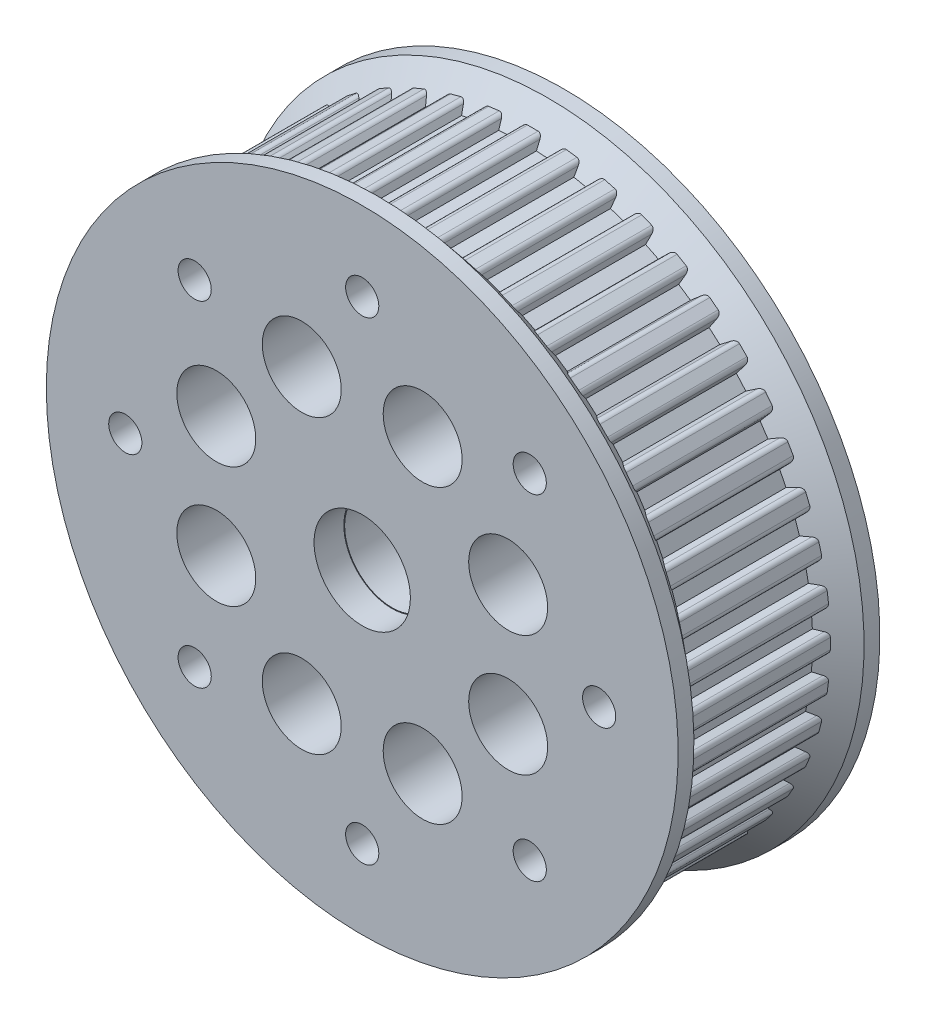
SolidWorks part; units mm, degrees
ref_plane "Plan de face" through (0, 0, 0) normal (0, 0, 1) x (1, 0, 0)
ref_plane "Plan de dessus" through (0, 0, 0) normal (0, 1, 0) x (1, 0, 0)
ref_plane "Plan de droite" through (0, 0, 0) normal (1, 0, 0) x (0, 0, -1)
sketch "Esquisse1" plane through (0, 0, 0) normal (0, 0, 1) x (1, 0, 0)
  line L0 (0, 0) -> (0, 38.195) construction
  line L1 (0, 0) -> (4.9854, 37.8682) construction
  line L2 (1.4855, 36.4258) -> (3.2817, 36.3081)
  line L3 (0, 0) -> (2.3836, 36.367) construction
  line L4 (0, 37.6783) -> (0.6704, 37.6783)
  line L5 (1.2464, 37.2462) -> (1.4855, 36.4258)
  line L6 (4.918, 37.356) -> (4.2534, 37.4435)
  line L7 (3.6259, 37.0903) -> (3.2817, 36.3081)
  line L8 (6.2274, 35.9203) -> (7.9928, 35.5691)
  line L9 (4.918, 37.356) -> (5.5827, 37.2685)
  line L10 (6.0974, 36.7649) -> (6.2274, 35.9203)
  line L11 (9.7519, 36.3945) -> (9.1043, 36.568)
  line L12 (8.4361, 36.2997) -> (7.9928, 35.5691)
  line L13 (10.8626, 34.8002) -> (12.5671, 34.2216)
  line L14 (9.7519, 36.3945) -> (10.3994, 36.221)
  line L15 (10.844, 35.6545) -> (10.8626, 34.8002)
  line L16 (14.4189, 34.8103) -> (13.7995, 35.0668)
  line L17 (13.102, 34.888) -> (12.5671, 34.2216)
  line L18 (15.312, 33.0846) -> (16.9264, 32.2885)
  line L19 (14.4189, 34.8103) -> (15.0382, 34.5537)
  line L20 (15.4051, 33.9341) -> (15.312, 33.0846)
  line L21 (18.8392, 32.6304) -> (18.2586, 32.9656)
  line L22 (17.5437, 32.8794) -> (16.9264, 32.2885)
  line L23 (19.4994, 30.8029) -> (20.9961, 29.8029)
  line L24 (18.8392, 32.6304) -> (19.4197, 32.2952)
  line L25 (19.7025, 31.633) -> (19.4994, 30.8029)
  line L26 (22.9371, 29.8922) -> (22.4053, 30.3003)
  line L27 (21.6852, 30.3082) -> (20.9961, 29.8029)
  line L28 (23.3532, 27.9942) -> (24.7065, 26.8074)
  line L29 (22.9371, 29.8922) -> (23.469, 29.4841)
  line L30 (23.6629, 28.7907) -> (23.3532, 27.9942)
  line L31 (26.6426, 26.6426) -> (26.1686, 27.1166)
  line L32 (25.4557, 27.2184) -> (24.7065, 26.8074)
  line L33 (26.8074, 24.7065) -> (27.9942, 23.3532)
  line L34 (26.6426, 26.6426) -> (27.1166, 26.1686)
  line L35 (27.2184, 25.4557) -> (26.8074, 24.7065)
  line L36 (29.8922, 22.9371) -> (29.4841, 23.469)
  line L37 (28.7907, 23.6629) -> (27.9942, 23.3532)
  line L38 (29.8029, 20.9961) -> (30.8029, 19.4994)
  line L39 (29.8922, 22.9371) -> (30.3003, 22.4053)
  line L40 (30.3082, 21.6852) -> (29.8029, 20.9961)
  line L41 (32.6304, 18.8392) -> (32.2952, 19.4197)
  line L42 (31.633, 19.7025) -> (30.8029, 19.4994)
  line L43 (32.2885, 16.9264) -> (33.0846, 15.312)
  line L44 (32.6304, 18.8392) -> (32.9656, 18.2586)
  line L45 (32.8794, 17.5437) -> (32.2885, 16.9264)
  line L46 (34.8103, 14.4189) -> (34.5537, 15.0382)
  line L47 (33.9341, 15.4051) -> (33.0846, 15.312)
  line L48 (34.2216, 12.5671) -> (34.8002, 10.8626)
  line L49 (34.8103, 14.4189) -> (35.0668, 13.7995)
  line L50 (34.888, 13.102) -> (34.2216, 12.5671)
  line L51 (36.3945, 9.7519) -> (36.221, 10.3994)
  line L52 (35.6545, 10.844) -> (34.8002, 10.8626)
  line L53 (35.5691, 7.9928) -> (35.9203, 6.2274)
  line L54 (36.3945, 9.7519) -> (36.568, 9.1043)
  line L55 (36.2997, 8.4361) -> (35.5691, 7.9928)
  line L56 (37.356, 4.918) -> (37.2685, 5.5827)
  line L57 (36.7649, 6.0974) -> (35.9203, 6.2274)
  line L58 (36.3081, 3.2817) -> (36.4258, 1.4855)
  line L59 (37.356, 4.918) -> (37.4435, 4.2534)
  line L60 (37.0903, 3.6259) -> (36.3081, 3.2817)
  line L61 (37.6783, 0) -> (37.6783, 0.6704)
  line L62 (37.2462, 1.2464) -> (36.4258, 1.4855)
  line L63 (36.4258, -1.4855) -> (36.3081, -3.2817)
  line L64 (37.6783, 0) -> (37.6783, -0.6704)
  line L65 (37.2462, -1.2464) -> (36.4258, -1.4855)
  line L66 (37.356, -4.918) -> (37.4435, -4.2534)
  line L67 (37.0903, -3.6259) -> (36.3081, -3.2817)
  line L68 (35.9203, -6.2274) -> (35.5691, -7.9928)
  line L69 (37.356, -4.918) -> (37.2685, -5.5827)
  line L70 (36.7649, -6.0974) -> (35.9203, -6.2274)
  line L71 (36.3945, -9.7519) -> (36.568, -9.1043)
  line L72 (36.2997, -8.4361) -> (35.5691, -7.9928)
  line L73 (34.8002, -10.8626) -> (34.2216, -12.5671)
  line L74 (36.3945, -9.7519) -> (36.221, -10.3994)
  line L75 (35.6545, -10.844) -> (34.8002, -10.8626)
  line L76 (34.8103, -14.4189) -> (35.0668, -13.7995)
  line L77 (34.888, -13.102) -> (34.2216, -12.5671)
  line L78 (33.0846, -15.312) -> (32.2885, -16.9264)
  line L79 (34.8103, -14.4189) -> (34.5537, -15.0382)
  line L80 (33.9341, -15.4051) -> (33.0846, -15.312)
  line L81 (32.6304, -18.8392) -> (32.9656, -18.2586)
  line L82 (32.8794, -17.5437) -> (32.2885, -16.9264)
  line L83 (30.8029, -19.4994) -> (29.8029, -20.9961)
  line L84 (32.6304, -18.8392) -> (32.2952, -19.4197)
  line L85 (31.633, -19.7025) -> (30.8029, -19.4994)
  line L86 (29.8922, -22.9371) -> (30.3003, -22.4053)
  line L87 (30.3082, -21.6852) -> (29.8029, -20.9961)
  line L88 (27.9942, -23.3532) -> (26.8074, -24.7065)
  line L89 (29.8922, -22.9371) -> (29.4841, -23.469)
  line L90 (28.7907, -23.6629) -> (27.9942, -23.3532)
  line L91 (26.6426, -26.6426) -> (27.1166, -26.1686)
  line L92 (27.2184, -25.4557) -> (26.8074, -24.7065)
  line L93 (24.7065, -26.8074) -> (23.3532, -27.9942)
  line L94 (26.6426, -26.6426) -> (26.1686, -27.1166)
  line L95 (25.4557, -27.2184) -> (24.7065, -26.8074)
  line L96 (22.9371, -29.8922) -> (23.469, -29.4841)
  line L97 (23.6629, -28.7907) -> (23.3532, -27.9942)
  line L98 (20.9961, -29.8029) -> (19.4994, -30.8029)
  line L99 (22.9371, -29.8922) -> (22.4053, -30.3003)
  line L100 (21.6852, -30.3082) -> (20.9961, -29.8029)
  line L101 (18.8392, -32.6304) -> (19.4197, -32.2952)
  line L102 (19.7025, -31.633) -> (19.4994, -30.8029)
  line L103 (16.9264, -32.2885) -> (15.312, -33.0846)
  line L104 (18.8392, -32.6304) -> (18.2586, -32.9656)
  line L105 (17.5437, -32.8794) -> (16.9264, -32.2885)
  line L106 (14.4189, -34.8103) -> (15.0382, -34.5537)
  line L107 (15.4051, -33.9341) -> (15.312, -33.0846)
  line L108 (12.5671, -34.2216) -> (10.8626, -34.8002)
  line L109 (14.4189, -34.8103) -> (13.7995, -35.0668)
  line L110 (13.102, -34.888) -> (12.5671, -34.2216)
  line L111 (9.7519, -36.3945) -> (10.3994, -36.221)
  line L112 (10.844, -35.6545) -> (10.8626, -34.8002)
  line L113 (7.9928, -35.5691) -> (6.2274, -35.9203)
  line L114 (9.7519, -36.3945) -> (9.1043, -36.568)
  line L115 (8.4361, -36.2997) -> (7.9928, -35.5691)
  line L116 (4.918, -37.356) -> (5.5827, -37.2685)
  line L117 (6.0974, -36.7649) -> (6.2274, -35.9203)
  line L118 (3.2817, -36.3081) -> (1.4855, -36.4258)
  line L119 (4.918, -37.356) -> (4.2534, -37.4435)
  line L120 (3.6259, -37.0903) -> (3.2817, -36.3081)
  line L121 (0, -37.6783) -> (0.6704, -37.6783)
  line L122 (1.2464, -37.2462) -> (1.4855, -36.4258)
  line L123 (-1.4855, -36.4258) -> (-3.2817, -36.3081)
  line L124 (0, -37.6783) -> (-0.6704, -37.6783)
  line L125 (-1.2464, -37.2462) -> (-1.4855, -36.4258)
  line L126 (-4.918, -37.356) -> (-4.2534, -37.4435)
  line L127 (-3.6259, -37.0903) -> (-3.2817, -36.3081)
  line L128 (-6.2274, -35.9203) -> (-7.9928, -35.5691)
  line L129 (-4.918, -37.356) -> (-5.5827, -37.2685)
  line L130 (-6.0974, -36.7649) -> (-6.2274, -35.9203)
  line L131 (-9.7519, -36.3945) -> (-9.1043, -36.568)
  line L132 (-8.4361, -36.2997) -> (-7.9928, -35.5691)
  line L133 (-10.8626, -34.8002) -> (-12.5671, -34.2216)
  line L134 (-9.7519, -36.3945) -> (-10.3994, -36.221)
  line L135 (-10.844, -35.6545) -> (-10.8626, -34.8002)
  line L136 (-14.4189, -34.8103) -> (-13.7995, -35.0668)
  line L137 (-13.102, -34.888) -> (-12.5671, -34.2216)
  line L138 (-15.312, -33.0846) -> (-16.9264, -32.2885)
  line L139 (-14.4189, -34.8103) -> (-15.0382, -34.5537)
  line L140 (-15.4051, -33.9341) -> (-15.312, -33.0846)
  line L141 (-18.8392, -32.6304) -> (-18.2586, -32.9656)
  line L142 (-17.5437, -32.8794) -> (-16.9264, -32.2885)
  line L143 (-19.4994, -30.8029) -> (-20.9961, -29.8029)
  line L144 (-18.8392, -32.6304) -> (-19.4197, -32.2952)
  line L145 (-19.7025, -31.633) -> (-19.4994, -30.8029)
  line L146 (-22.9371, -29.8922) -> (-22.4053, -30.3003)
  line L147 (-21.6852, -30.3082) -> (-20.9961, -29.8029)
  line L148 (-23.3532, -27.9942) -> (-24.7065, -26.8074)
  line L149 (-22.9371, -29.8922) -> (-23.469, -29.4841)
  line L150 (-23.6629, -28.7907) -> (-23.3532, -27.9942)
  line L151 (-26.6426, -26.6426) -> (-26.1686, -27.1166)
  line L152 (-25.4557, -27.2184) -> (-24.7065, -26.8074)
  line L153 (-26.8074, -24.7065) -> (-27.9942, -23.3532)
  line L154 (-26.6426, -26.6426) -> (-27.1166, -26.1686)
  line L155 (-27.2184, -25.4557) -> (-26.8074, -24.7065)
  line L156 (-29.8922, -22.9371) -> (-29.4841, -23.469)
  line L157 (-28.7907, -23.6629) -> (-27.9942, -23.3532)
  line L158 (-29.8029, -20.9961) -> (-30.8029, -19.4994)
  line L159 (-29.8922, -22.9371) -> (-30.3003, -22.4053)
  line L160 (-30.3082, -21.6852) -> (-29.8029, -20.9961)
  line L161 (-32.6304, -18.8392) -> (-32.2952, -19.4197)
  line L162 (-31.633, -19.7025) -> (-30.8029, -19.4994)
  line L163 (-32.2885, -16.9264) -> (-33.0846, -15.312)
  line L164 (-32.6304, -18.8392) -> (-32.9656, -18.2586)
  line L165 (-32.8794, -17.5437) -> (-32.2885, -16.9264)
  line L166 (-34.8103, -14.4189) -> (-34.5537, -15.0382)
  line L167 (-33.9341, -15.4051) -> (-33.0846, -15.312)
  line L168 (-34.2216, -12.5671) -> (-34.8002, -10.8626)
  line L169 (-34.8103, -14.4189) -> (-35.0668, -13.7995)
  line L170 (-34.888, -13.102) -> (-34.2216, -12.5671)
  line L171 (-36.3945, -9.7519) -> (-36.221, -10.3994)
  line L172 (-35.6545, -10.844) -> (-34.8002, -10.8626)
  line L173 (-35.5691, -7.9928) -> (-35.9203, -6.2274)
  line L174 (-36.3945, -9.7519) -> (-36.568, -9.1043)
  line L175 (-36.2997, -8.4361) -> (-35.5691, -7.9928)
  line L176 (-37.356, -4.918) -> (-37.2685, -5.5827)
  line L177 (-36.7649, -6.0974) -> (-35.9203, -6.2274)
  line L178 (-36.3081, -3.2817) -> (-36.4258, -1.4855)
  line L179 (-37.356, -4.918) -> (-37.4435, -4.2534)
  line L180 (-37.0903, -3.6259) -> (-36.3081, -3.2817)
  line L181 (-37.6783, 0) -> (-37.6783, -0.6704)
  line L182 (-37.2462, -1.2464) -> (-36.4258, -1.4855)
  line L183 (-36.4258, 1.4855) -> (-36.3081, 3.2817)
  line L184 (-37.6783, 0) -> (-37.6783, 0.6704)
  line L185 (-37.2462, 1.2464) -> (-36.4258, 1.4855)
  line L186 (-37.356, 4.918) -> (-37.4435, 4.2534)
  line L187 (-37.0903, 3.6259) -> (-36.3081, 3.2817)
  line L188 (-35.9203, 6.2274) -> (-35.5691, 7.9928)
  line L189 (-37.356, 4.918) -> (-37.2685, 5.5827)
  line L190 (-36.7649, 6.0974) -> (-35.9203, 6.2274)
  line L191 (-36.3945, 9.7519) -> (-36.568, 9.1043)
  line L192 (-36.2997, 8.4361) -> (-35.5691, 7.9928)
  line L193 (-34.8002, 10.8626) -> (-34.2216, 12.5671)
  line L194 (-36.3945, 9.7519) -> (-36.221, 10.3994)
  line L195 (-35.6545, 10.844) -> (-34.8002, 10.8626)
  line L196 (-34.8103, 14.4189) -> (-35.0668, 13.7995)
  line L197 (-34.888, 13.102) -> (-34.2216, 12.5671)
  line L198 (-33.0846, 15.312) -> (-32.2885, 16.9264)
  line L199 (-34.8103, 14.4189) -> (-34.5537, 15.0382)
  line L200 (-33.9341, 15.4051) -> (-33.0846, 15.312)
  line L201 (-32.6304, 18.8392) -> (-32.9656, 18.2586)
  line L202 (-32.8794, 17.5437) -> (-32.2885, 16.9264)
  line L203 (-30.8029, 19.4994) -> (-29.8029, 20.9961)
  line L204 (-32.6304, 18.8392) -> (-32.2952, 19.4197)
  line L205 (-31.633, 19.7025) -> (-30.8029, 19.4994)
  line L206 (-29.8922, 22.9371) -> (-30.3003, 22.4053)
  line L207 (-30.3082, 21.6852) -> (-29.8029, 20.9961)
  line L208 (-27.9942, 23.3532) -> (-26.8074, 24.7065)
  line L209 (-29.8922, 22.9371) -> (-29.4841, 23.469)
  line L210 (-28.7907, 23.6629) -> (-27.9942, 23.3532)
  line L211 (-26.6426, 26.6426) -> (-27.1166, 26.1686)
  line L212 (-27.2184, 25.4557) -> (-26.8074, 24.7065)
  line L213 (-24.7065, 26.8074) -> (-23.3532, 27.9942)
  line L214 (-26.6426, 26.6426) -> (-26.1686, 27.1166)
  line L215 (-25.4557, 27.2184) -> (-24.7065, 26.8074)
  line L216 (-22.9371, 29.8922) -> (-23.469, 29.4841)
  line L217 (-23.6629, 28.7907) -> (-23.3532, 27.9942)
  line L218 (-20.9961, 29.8029) -> (-19.4994, 30.8029)
  line L219 (-22.9371, 29.8922) -> (-22.4053, 30.3003)
  line L220 (-21.6852, 30.3082) -> (-20.9961, 29.8029)
  line L221 (-18.8392, 32.6304) -> (-19.4197, 32.2952)
  line L222 (-19.7025, 31.633) -> (-19.4994, 30.8029)
  line L223 (-16.9264, 32.2885) -> (-15.312, 33.0846)
  line L224 (-18.8392, 32.6304) -> (-18.2586, 32.9656)
  line L225 (-17.5437, 32.8794) -> (-16.9264, 32.2885)
  line L226 (-14.4189, 34.8103) -> (-15.0382, 34.5537)
  line L227 (-15.4051, 33.9341) -> (-15.312, 33.0846)
  line L228 (-12.5671, 34.2216) -> (-10.8626, 34.8002)
  line L229 (-14.4189, 34.8103) -> (-13.7995, 35.0668)
  line L230 (-13.102, 34.888) -> (-12.5671, 34.2216)
  line L231 (-9.7519, 36.3945) -> (-10.3994, 36.221)
  line L232 (-10.844, 35.6545) -> (-10.8626, 34.8002)
  line L233 (-7.9928, 35.5691) -> (-6.2274, 35.9203)
  line L234 (-9.7519, 36.3945) -> (-9.1043, 36.568)
  line L235 (-8.4361, 36.2997) -> (-7.9928, 35.5691)
  line L236 (-4.918, 37.356) -> (-5.5827, 37.2685)
  line L237 (-6.0974, 36.7649) -> (-6.2274, 35.9203)
  line L238 (-3.2817, 36.3081) -> (-1.4855, 36.4258)
  line L239 (-4.918, 37.356) -> (-4.2534, 37.4435)
  line L240 (-3.6259, 37.0903) -> (-3.2817, 36.3081)
  line L241 (0, 37.6783) -> (-0.6704, 37.6783)
  line L242 (-1.2464, 37.2462) -> (-1.4855, 36.4258)
  circle A0 centre (0, 0) radius 38.195 construction
  circle A1 centre (0, 0) radius 37.695 construction
  circle A2 centre (0, 0) radius 36.445 construction
  arc A3 (4.2534, 37.4435) -> (3.6259, 37.0903) centre (4.175, 36.8486) ccw
  arc A4 (1.2464, 37.2462) -> (0.6704, 37.6783) centre (0.6704, 37.0783) ccw
  arc A5 (9.1043, 36.568) -> (8.4361, 36.2997) centre (8.949, 35.9884) ccw
  arc A6 (6.0974, 36.7649) -> (5.5827, 37.2685) centre (5.5043, 36.6736) ccw
  arc A7 (13.7995, 35.0668) -> (13.102, 34.888) centre (13.5699, 34.5125) ccw
  arc A8 (10.844, 35.6545) -> (10.3994, 36.221) centre (10.2441, 35.6414) ccw
  arc A9 (18.2586, 32.9656) -> (17.5437, 32.8794) centre (17.9586, 32.446) ccw
  arc A10 (15.4051, 33.9341) -> (15.0382, 34.5537) centre (14.8086, 33.9994) ccw
  arc A11 (22.4053, 30.3003) -> (21.6852, 30.3082) centre (22.04, 29.8243) ccw
  arc A12 (19.7025, 31.633) -> (19.4197, 32.2952) centre (19.1197, 31.7756) ccw
  arc A13 (26.1686, 27.1166) -> (25.4557, 27.2184) centre (25.7443, 26.6924) ccw
  arc A14 (23.6629, 28.7907) -> (23.469, 29.4841) centre (23.1037, 29.0081) ccw
  arc A15 (29.4841, 23.469) -> (28.7907, 23.6629) centre (29.0081, 23.1037) ccw
  arc A16 (27.2184, 25.4557) -> (27.1166, 26.1686) centre (26.6924, 25.7443) ccw
  arc A17 (32.2952, 19.4197) -> (31.633, 19.7025) centre (31.7756, 19.1197) ccw
  arc A18 (30.3082, 21.6852) -> (30.3003, 22.4053) centre (29.8243, 22.04) ccw
  arc A19 (34.5537, 15.0382) -> (33.9341, 15.4051) centre (33.9994, 14.8086) ccw
  arc A20 (32.8794, 17.5437) -> (32.9656, 18.2586) centre (32.446, 17.9586) ccw
  arc A21 (36.221, 10.3994) -> (35.6545, 10.844) centre (35.6414, 10.2441) ccw
  arc A22 (34.888, 13.102) -> (35.0668, 13.7995) centre (34.5125, 13.5699) ccw
  arc A23 (37.2685, 5.5827) -> (36.7649, 6.0974) centre (36.6736, 5.5043) ccw
  arc A24 (36.2997, 8.4361) -> (36.568, 9.1043) centre (35.9884, 8.949) ccw
  arc A25 (37.6783, 0.6704) -> (37.2462, 1.2464) centre (37.0783, 0.6704) ccw
  arc A26 (37.0903, 3.6259) -> (37.4435, 4.2534) centre (36.8486, 4.175) ccw
  arc A27 (37.4435, -4.2534) -> (37.0903, -3.6259) centre (36.8486, -4.175) ccw
  arc A28 (37.2462, -1.2464) -> (37.6783, -0.6704) centre (37.0783, -0.6704) ccw
  arc A29 (36.568, -9.1043) -> (36.2997, -8.4361) centre (35.9884, -8.949) ccw
  arc A30 (36.7649, -6.0974) -> (37.2685, -5.5827) centre (36.6736, -5.5043) ccw
  arc A31 (35.0668, -13.7995) -> (34.888, -13.102) centre (34.5125, -13.5699) ccw
  arc A32 (35.6545, -10.844) -> (36.221, -10.3994) centre (35.6414, -10.2441) ccw
  arc A33 (32.9656, -18.2586) -> (32.8794, -17.5437) centre (32.446, -17.9586) ccw
  arc A34 (33.9341, -15.4051) -> (34.5537, -15.0382) centre (33.9994, -14.8086) ccw
  arc A35 (30.3003, -22.4053) -> (30.3082, -21.6852) centre (29.8243, -22.04) ccw
  arc A36 (31.633, -19.7025) -> (32.2952, -19.4197) centre (31.7756, -19.1197) ccw
  arc A37 (27.1166, -26.1686) -> (27.2184, -25.4557) centre (26.6924, -25.7443) ccw
  arc A38 (28.7907, -23.6629) -> (29.4841, -23.469) centre (29.0081, -23.1037) ccw
  arc A39 (23.469, -29.4841) -> (23.6629, -28.7907) centre (23.1037, -29.0081) ccw
  arc A40 (25.4557, -27.2184) -> (26.1686, -27.1166) centre (25.7443, -26.6924) ccw
  arc A41 (19.4197, -32.2952) -> (19.7025, -31.633) centre (19.1197, -31.7756) ccw
  arc A42 (21.6852, -30.3082) -> (22.4053, -30.3003) centre (22.04, -29.8243) ccw
  arc A43 (15.0382, -34.5537) -> (15.4051, -33.9341) centre (14.8086, -33.9994) ccw
  arc A44 (17.5437, -32.8794) -> (18.2586, -32.9656) centre (17.9586, -32.446) ccw
  arc A45 (10.3994, -36.221) -> (10.844, -35.6545) centre (10.2441, -35.6414) ccw
  arc A46 (13.102, -34.888) -> (13.7995, -35.0668) centre (13.5699, -34.5125) ccw
  arc A47 (5.5827, -37.2685) -> (6.0974, -36.7649) centre (5.5043, -36.6736) ccw
  arc A48 (8.4361, -36.2997) -> (9.1043, -36.568) centre (8.949, -35.9884) ccw
  arc A49 (0.6704, -37.6783) -> (1.2464, -37.2462) centre (0.6704, -37.0783) ccw
  arc A50 (3.6259, -37.0903) -> (4.2534, -37.4435) centre (4.175, -36.8486) ccw
  arc A51 (-4.2534, -37.4435) -> (-3.6259, -37.0903) centre (-4.175, -36.8486) ccw
  arc A52 (-1.2464, -37.2462) -> (-0.6704, -37.6783) centre (-0.6704, -37.0783) ccw
  arc A53 (-9.1043, -36.568) -> (-8.4361, -36.2997) centre (-8.949, -35.9884) ccw
  arc A54 (-6.0974, -36.7649) -> (-5.5827, -37.2685) centre (-5.5043, -36.6736) ccw
  arc A55 (-13.7995, -35.0668) -> (-13.102, -34.888) centre (-13.5699, -34.5125) ccw
  arc A56 (-10.844, -35.6545) -> (-10.3994, -36.221) centre (-10.2441, -35.6414) ccw
  arc A57 (-18.2586, -32.9656) -> (-17.5437, -32.8794) centre (-17.9586, -32.446) ccw
  arc A58 (-15.4051, -33.9341) -> (-15.0382, -34.5537) centre (-14.8086, -33.9994) ccw
  arc A59 (-22.4053, -30.3003) -> (-21.6852, -30.3082) centre (-22.04, -29.8243) ccw
  arc A60 (-19.7025, -31.633) -> (-19.4197, -32.2952) centre (-19.1197, -31.7756) ccw
  arc A61 (-26.1686, -27.1166) -> (-25.4557, -27.2184) centre (-25.7443, -26.6924) ccw
  arc A62 (-23.6629, -28.7907) -> (-23.469, -29.4841) centre (-23.1037, -29.0081) ccw
  arc A63 (-29.4841, -23.469) -> (-28.7907, -23.6629) centre (-29.0081, -23.1037) ccw
  arc A64 (-27.2184, -25.4557) -> (-27.1166, -26.1686) centre (-26.6924, -25.7443) ccw
  arc A65 (-32.2952, -19.4197) -> (-31.633, -19.7025) centre (-31.7756, -19.1197) ccw
  arc A66 (-30.3082, -21.6852) -> (-30.3003, -22.4053) centre (-29.8243, -22.04) ccw
  arc A67 (-34.5537, -15.0382) -> (-33.9341, -15.4051) centre (-33.9994, -14.8086) ccw
  arc A68 (-32.8794, -17.5437) -> (-32.9656, -18.2586) centre (-32.446, -17.9586) ccw
  arc A69 (-36.221, -10.3994) -> (-35.6545, -10.844) centre (-35.6414, -10.2441) ccw
  arc A70 (-34.888, -13.102) -> (-35.0668, -13.7995) centre (-34.5125, -13.5699) ccw
  arc A71 (-37.2685, -5.5827) -> (-36.7649, -6.0974) centre (-36.6736, -5.5043) ccw
  arc A72 (-36.2997, -8.4361) -> (-36.568, -9.1043) centre (-35.9884, -8.949) ccw
  arc A73 (-37.6783, -0.6704) -> (-37.2462, -1.2464) centre (-37.0783, -0.6704) ccw
  arc A74 (-37.0903, -3.6259) -> (-37.4435, -4.2534) centre (-36.8486, -4.175) ccw
  arc A75 (-37.4435, 4.2534) -> (-37.0903, 3.6259) centre (-36.8486, 4.175) ccw
  arc A76 (-37.2462, 1.2464) -> (-37.6783, 0.6704) centre (-37.0783, 0.6704) ccw
  arc A77 (-36.568, 9.1043) -> (-36.2997, 8.4361) centre (-35.9884, 8.949) ccw
  arc A78 (-36.7649, 6.0974) -> (-37.2685, 5.5827) centre (-36.6736, 5.5043) ccw
  arc A79 (-35.0668, 13.7995) -> (-34.888, 13.102) centre (-34.5125, 13.5699) ccw
  arc A80 (-35.6545, 10.844) -> (-36.221, 10.3994) centre (-35.6414, 10.2441) ccw
  arc A81 (-32.9656, 18.2586) -> (-32.8794, 17.5437) centre (-32.446, 17.9586) ccw
  arc A82 (-33.9341, 15.4051) -> (-34.5537, 15.0382) centre (-33.9994, 14.8086) ccw
  arc A83 (-30.3003, 22.4053) -> (-30.3082, 21.6852) centre (-29.8243, 22.04) ccw
  arc A84 (-31.633, 19.7025) -> (-32.2952, 19.4197) centre (-31.7756, 19.1197) ccw
  arc A85 (-27.1166, 26.1686) -> (-27.2184, 25.4557) centre (-26.6924, 25.7443) ccw
  arc A86 (-28.7907, 23.6629) -> (-29.4841, 23.469) centre (-29.0081, 23.1037) ccw
  arc A87 (-23.469, 29.4841) -> (-23.6629, 28.7907) centre (-23.1037, 29.0081) ccw
  arc A88 (-25.4557, 27.2184) -> (-26.1686, 27.1166) centre (-25.7443, 26.6924) ccw
  arc A89 (-19.4197, 32.2952) -> (-19.7025, 31.633) centre (-19.1197, 31.7756) ccw
  arc A90 (-21.6852, 30.3082) -> (-22.4053, 30.3003) centre (-22.04, 29.8243) ccw
  arc A91 (-15.0382, 34.5537) -> (-15.4051, 33.9341) centre (-14.8086, 33.9994) ccw
  arc A92 (-17.5437, 32.8794) -> (-18.2586, 32.9656) centre (-17.9586, 32.446) ccw
  arc A93 (-10.3994, 36.221) -> (-10.844, 35.6545) centre (-10.2441, 35.6414) ccw
  arc A94 (-13.102, 34.888) -> (-13.7995, 35.0668) centre (-13.5699, 34.5125) ccw
  arc A95 (-5.5827, 37.2685) -> (-6.0974, 36.7649) centre (-5.5043, 36.6736) ccw
  arc A96 (-8.4361, 36.2997) -> (-9.1043, 36.568) centre (-8.949, 35.9884) ccw
  arc A97 (-0.6704, 37.6783) -> (-1.2464, 37.2462) centre (-0.6704, 37.0783) ccw
  arc A98 (-3.6259, 37.0903) -> (-4.2534, 37.4435) centre (-4.175, 36.8486) ccw
  circle A99 centre (0, 0) radius 6
  point P22 (3.8071, 37.5023)
  point P25 (1.1205, 37.6783)
  point P492 (0, 0)
  dimension "D1" = 76.39
  dimension "D3" = 0.5
  dimension "D4" = 1.25
  dimension "D9" = 0.6
  dimension "D11" = 12
  dimension "D2" = 7.5
  dimension "D5" = 3.75
  dimension "D6" = 20
  dimension "D7" = 20
  dimension "D8" = 1.8
  dimension "D10" = 48
extrude "Boss.-Extru.1" add sketch "Esquisse1" along normal blind 18
sketch "Esquisse2" plane through (0, 0, 0) normal (0, 1, 0) x (1, 0, 0)
  line L0 (0, 0) -> (0, -18) construction
  line L1 (0.6704, -18) -> (-0.6704, -18) construction
  line L2 (-6.1, -23.7725) -> (-6.1, 5.7725)
  line L3 (-6.1, 5.7725) -> (-8.6, 5.7725)
  line L4 (-8.6, 5.7725) -> (-8.6, 3.7725)
  line L5 (-8.6, 3.7725) -> (-40, 3.7725)
  line L6 (-40, 3.7725) -> (-40, 1.7725)
  line L7 (-40, 1.7725) -> (-36.1, -1.5)
  line L8 (-36.1, -1.5) -> (-36.1, -16.5)
  line L9 (-36.1, -16.5) -> (-40, -19.7725)
  line L10 (-40, -19.7725) -> (-40, -21.7725)
  line L11 (-40, -21.7725) -> (-8.6, -21.7725)
  line L12 (-8.6, -21.7725) -> (-8.6, -23.7725)
  line L13 (-8.6, -23.7725) -> (-6.1, -23.7725)
  line L14 (-36.1, -9) -> (-6.1, -9) construction
  point P15 (0, -9)
  point P20 (-10.3202, 4.5483)
  dimension "D1" = 15
  dimension "D2" = 40
  dimension "D3" = 40
  dimension "D4" = 30
  dimension "D5" = 6.1
  dimension "D6" = 40
  dimension "D7" = 2
  dimension "D8" = 2
  dimension "D9" = 2
  dimension "D10" = 2.5
revolve "Révolution1" add sketch "Esquisse2" angle 360 about L0
sketch "Esquisse3" plane through (0, 0, -3.7725) normal (0, 0, -1) x (-1, 0, 0)
  circle A0 centre (0, 0) radius 30 construction
  circle A1 centre (0, 30) radius 2.1
  circle A2 centre (21.2132, 21.2132) radius 2.1
  circle A3 centre (30, 0) radius 2.1
  circle A4 centre (21.2132, -21.2132) radius 2.1
  circle A5 centre (0, -30) radius 2.1
  circle A6 centre (-21.2132, -21.2132) radius 2.1
  circle A7 centre (-30, 0) radius 2.1
  circle A8 centre (-21.2132, 21.2132) radius 2.1
  point P21 (0, 0)
  dimension "D1" = 60
  dimension "D2" = 4.2
  dimension "D3" = 8
extrude "Enlèv. mat.-Extru.1" cut sketch "Esquisse3" against normal through all
sketch "Esquisse4" plane through (0, 0, -3.7725) normal (0, 0, -1) x (-1, 0, 0)
  line L0 (0, 0) -> (40, 0) construction
  line L2 (15, 1.5) -> (-15, 1.5)
  line L3 (15, 1.5) -> (15, -1.5)
  line L4 (15, -1.5) -> (-15, -1.5)
  line L5 (-15, 1.5) -> (-15, -1.5)
  line L6 (15, 1.5) -> (-15, -1.5) construction
  line L7 (15, -1.5) -> (-15, 1.5) construction
  circle A0 centre (0, 0) radius 40 construction
  dimension "D1" = 3
  dimension "D2" = 30
extrude "Enlèv. mat.-Extru.2" cut sketch "Esquisse4" against normal blind 12 and the other way blind 12
sketch "Esquisse5" plane through (0, 0, 23.7725) normal (0, 0, 1) x (1, 0, 0)
  circle A0 centre (0, 0) radius 6.1 construction
  circle A1 centre (0, 0) radius 8.6
  circle A2 centre (0, 0) radius 8.6
  circle A3 centre (0, 0) radius 6.1
  dimension "D1" = 0
extrude "Enlèv. mat.-Extru.3" cut sketch "Esquisse5" against normal blind 2
sketch "Esquisse6" plane through (0, 0, -3.7725) normal (0, 0, -1) x (-1, 0, 0)
  line L0 (0, 0) -> (0, -30) construction
  line L1 (0, 0) -> (7.6537, -18.4776) construction
  circle A0 centre (0, 0) radius 20 construction
  circle A1 centre (7.6537, -18.4776) radius 5
  circle A2 centre (-7.6537, -18.4776) radius 5
  circle A3 centre (-18.4776, -7.6537) radius 5
  circle A4 centre (-18.4776, 7.6537) radius 5
  circle A5 centre (-7.6537, 18.4776) radius 5
  circle A6 centre (7.6537, 18.4776) radius 5
  circle A7 centre (18.4776, 7.6537) radius 5
  circle A8 centre (18.4776, -7.6537) radius 5
  point P24 (0, 0)
  dimension "D1" = 40
  dimension "D2" = 10
  dimension "D3" = 22.5
  dimension "D4" = 8
extrude "Enlèv. mat.-Extru.4" cut sketch "Esquisse6" against normal through all
